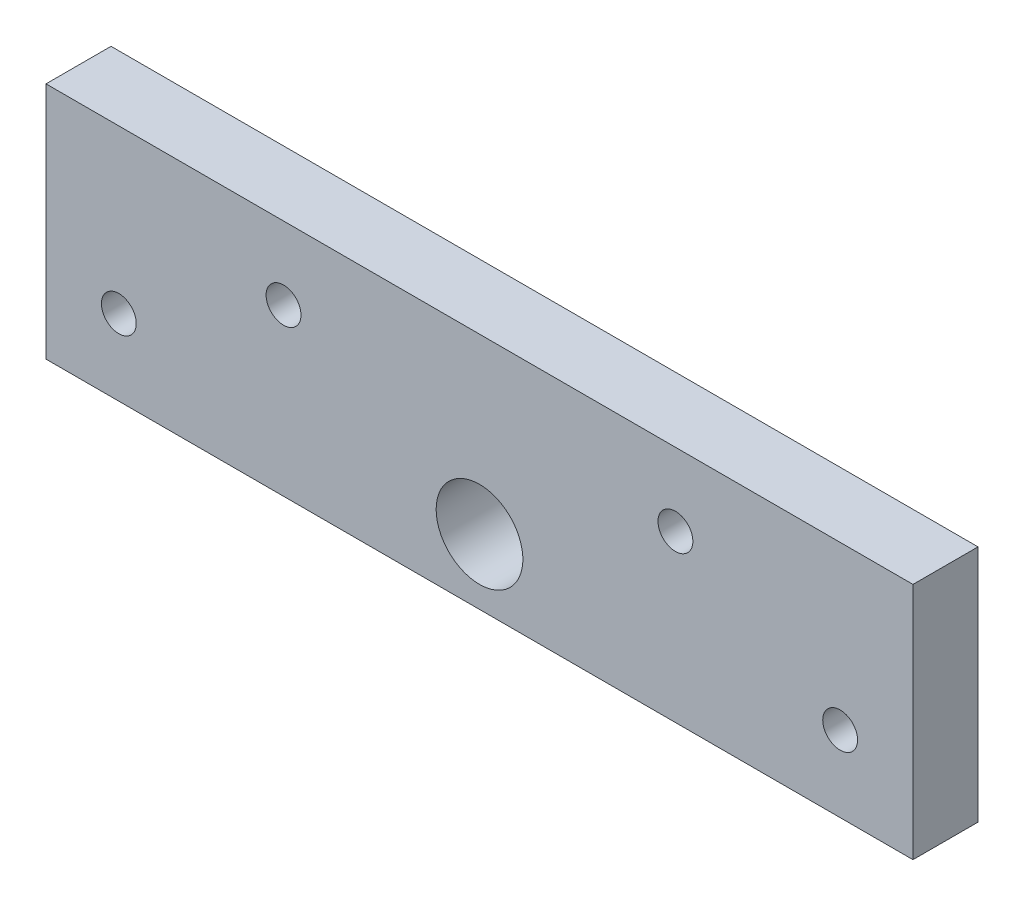
SolidWorks part; units mm, degrees
material "6061-T6 (SS)"
ref_plane "Front Plane" through (0, 0, 0) normal (0, 0, 1) x (1, 0, 0)
ref_plane "Top Plane" through (0, 0, 0) normal (0, 1, 0) x (1, 0, 0)
ref_plane "Right Plane" through (0, 0, 0) normal (1, 0, 0) x (0, 0, -1)
sketch "Sketch8" plane through (0, 0, 0) normal (0, 0, 1) x (1, 0, 0)
  line B0 (-63.5, -15.875) -> (63.5, -15.875)
  line B1 (63.5, -15.875) -> (63.5, 0)
  line B2 (38.4596, 0) -> (47.625, 15.875)
  line B3 (47.625, 15.875) -> (16.0563, 15.875)
  line B4 (-40.2927, 15.875) -> (-31.1272, 0)
  line B5 (-31.1272, 0) -> (-63.5, 0)
  line B6 (-38.4596, 0) -> (-47.625, 15.875)
  line B7 (-47.625, 15.875) -> (-40.2927, 15.875)
  line B8 (-16.0563, 15.875) -> (-16.0563, -3.175) construction
  line B9 (-16.0563, -3.175) -> (16.0563, -3.175) construction
  line B10 (16.0563, -3.175) -> (16.0563, 15.875) construction
  line B11 (-16.0563, 15.875) -> (-40.2927, 15.875)
  line B12 (-63.5, 0) -> (-63.5, 31.75)
  line B13 (-63.5, 31.75) -> (63.5, 31.75)
  line B14 (-16.0563, 15.875) -> (16.0563, 15.875) construction
  line B15 (0, 31.75) -> (0, -15.875) construction
  line B16 (-38.4596, 0) -> (38.4596, 0) construction
  line B17 (-28.702, 21.082) -> (28.702, 21.082) construction
  line B18 (-25.4, -8.001) -> (25.4, -8.001) construction
  line B19 (-25.4, -8.001) -> (-25.4, 7.9375) construction
  line B20 (-52.832, 7.9375) -> (52.832, 7.9375) construction
  circle B21 centre (0, 6.35) radius 18.669 construction
  line B22 (40.2927, 15.875) -> (31.1272, 0)
sketch_block_instance "dovetail pair-1"
sketch_block "Block1" parameters "D8"=37.338, "D1"=60, "D2"=127, "D3"=6.35, "D4"=15.875, "D5"=31.75, "D6"=95.25, "D7"=19.05, "D9"=60, "D10"=31.75, "D11"=50.8, "D12"=23.876, "D13"=7.874, "D14"=10.668, "D15"=34.798, "D16"=21.082, "D17"=7.9375, "D18"=24.4437
sketch "Sketch1" plane through (0, 0, 0) normal (0, 0, 1) x (1, 0, 0)
  line L0 (63.5, -15.875) -> (63.5, 0) construction
  line L1 (-63.5, 31.75) -> (63.5, 31.75)
  line L2 (-63.5, 31.75) -> (-63.5, -3.175)
  line L3 (-63.5, -3.175) -> (63.5, -3.175)
  line L4 (63.5, 31.75) -> (63.5, -3.175)
  line L5 (-16.0563, -3.175) -> (16.0563, -3.175) construction
  circle A0 centre (0, 6.35) radius 6.35
  dimension "D1" = 12.7
extrude "Boss-Extrude1" add sketch "Sketch1" along normal blind 9.525
hole_wizard "CBORE for #10 Socket Head Cap Screw1" positions "Sketch6" profile "Sketch7" counterbore size "#10" standard "ANSI Inch" end condition up to next
sketch "Sketch6" plane through (248.3324, -44.45, 0) normal (0, 0, -1) x (-1, 0, 0)
  point P26 (219.6304, 65.532)
  point P28 (195.5004, 52.3875)
  point P30 (277.0344, 65.532)
  point P32 (301.1644, 52.3875)
sketch "Sketch7" plane through (28.702, 21.082, 0) normal (1, 0, 0) x (0, 1, 0)
  line L0 (0, 0) -> (0, 9.525)
  line L1 (0, 9.525) -> (2.5527, 9.525)
  line L3 (2.5527, 9.525) -> (2.5527, 4.826)
  line L4 (4.7625, 4.826) -> (2.5527, 4.826)
  line L5 (4.7625, 4.826) -> (4.7625, 0.635)
  line L6 (4.7625, 0.635) -> (5.3975, 0)
  line L7 (5.3975, 0) -> (0, 0)
  line L8 (-4.7625, 0.635) -> (-5.3975, 0) construction
  line L11 (0, -6.35) -> (0, 107.95) construction
  dimension "Thru Hole Dia." = 5.1054
  dimension "Thru Hole Depth" = 9.525
  dimension "C'Bore Dia." = 9.525
  dimension "C'Bore Depth" = 4.826
  dimension "Near C'Sink Dia." = 10.795
  dimension "Near C'Sink Angle" = 90
equation "\"dovetail-angle\"= 60"
equation "\"dovetail-stock-width\"= 5"
equation "\"dovetail-stock-height\"= 1.25"
equation "\"dovetail-depth\"= 0.5 * \"dovetail-stock-height\""
equation "\"dovetail-throat-width\"= \"dovetail-stock-width\" - (2 * \"dovetail-depth\")"
equation "\"delta-x\"= 6"
equation "\"delta-y\"= 3"
equation "\"gib-thickness\"= 0.25"
equation "\"x-slide-length\"= \"dovetail-stock-width\" + \"delta-x\""
equation "\"y-slide-length\"= \"dovetail-stock-width\" + \"delta-y\""
equation "\"dog-point-diam\"= .149"
equation "\"dog-point-length\"= .067"
equation "\"dovetail-double-height\"= 2 * \"dovetail-depth\" + 0.5"
equation "\"acme-major-diam\"= .5"
equation "\"acme-pitch-diam\"= 0.45"
equation "\"acme-minor-diam\"= 0.4"
equation "\"x-screw-length\"= \"x-slide-length\" + \"screw-add-length\""
equation "\"y-screw-length\"= \"y-slide-length\" + \"screw-add-length\""
equation "\"acme-nut-od\"= 1.47"
equation "\"acme-nut-length\"= 1"
equation "\"acme-nut-trim-height\"= .75"
equation "\"D1@Sketch1\"=\"screw-bearing-od\""
equation "\"screw-bearing-od\"= 0.5"
equation "\"screw-bearing-length\"= .375"
equation "\"end-plate-thickness\"= \"screw-bearing-length\""
equation "\"D1@Boss-Extrude1\"=\"end-plate-thickness\""
equation "\"screw-bearing-id\"= .375"
equation "\"screw-add-length\"= 2 * \"end-plate-thickness\" + 1 + 0.5"
equation "\"acme-nut-mount-hole-space-horz\"= 0.95"
equation "\"acme-nut-mount-hole-space-vert\"= 0.5 * \"acme-nut-length\""
